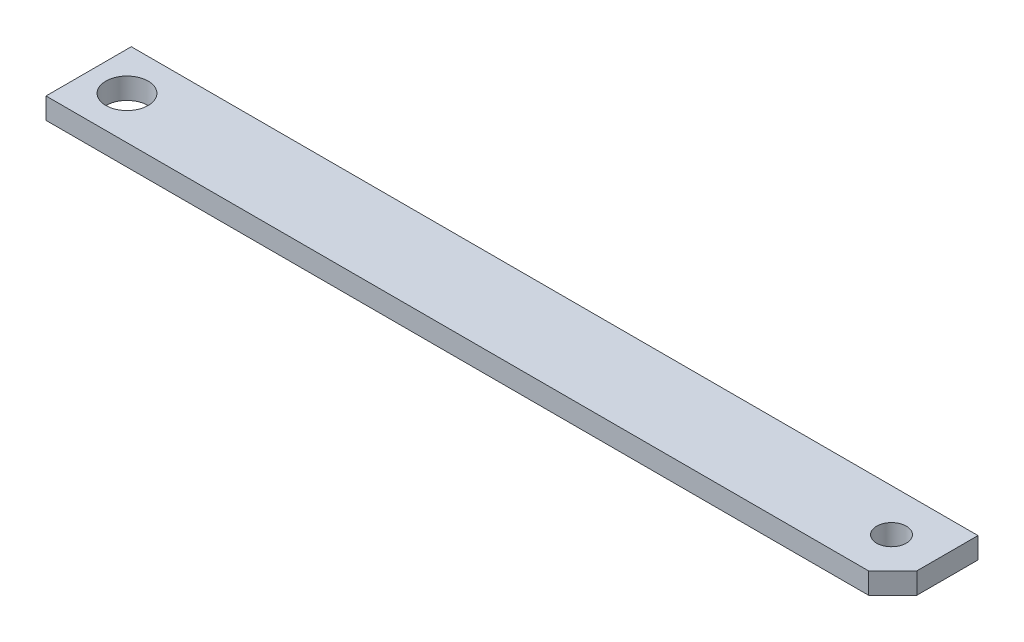
SolidWorks part; units mm, degrees
material "ABS PC"
ref_plane "Płaszczyzna przednia" through (0, 0, 0) normal (0, 0, 1) x (1, 0, 0)
ref_plane "Płaszczyzna górna" through (0, 0, 0) normal (0, 1, 0) x (1, 0, 0)
ref_plane "Płaszczyzna prawa" through (0, 0, 0) normal (1, 0, 0) x (0, 0, -1)
sketch "Szkic1" plane through (0, 0, 0) normal (0, 1, 0) x (1, 0, 0)
  line L0 (370.5962, -20.2173) -> (381.9909, -8.8226)
  line L5 (-18.0473, 20.0822) -> (381.9909, 20.0822)
  line L6 (-18.0473, 20.0822) -> (-18.0473, -20.2173)
  line L7 (-18.0473, -20.2173) -> (370.5962, -20.2173)
  line L8 (381.9909, 20.0822) -> (381.9909, -8.8226)
  circle A0 centre (0, 0) radius 10
  circle A1 centre (361.2, 0) radius 7
  circle A2 centre (0, 0) radius 27 construction
  dimension "D2" = 20
  dimension "D3" = 14
  dimension "D1" = 361.2
extrude "Dodanie-wyciągnięcie1" add sketch "Szkic1" along normal blind 10
